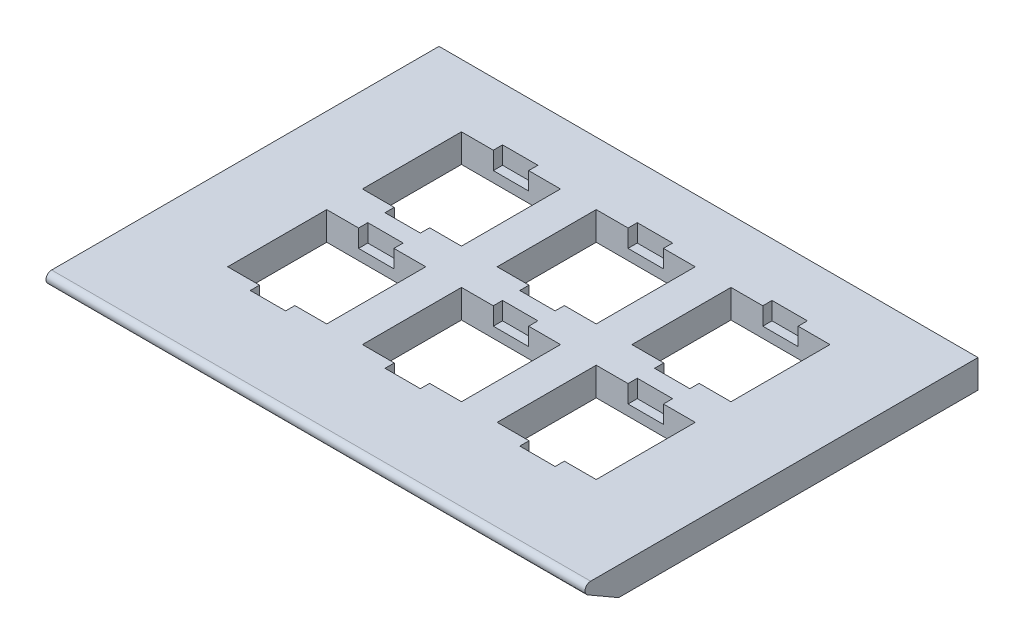
SolidWorks part; units mm, degrees
ref_plane "Front Plane" through (0, 0, 0) normal (0, 0, 1) x (1, 0, 0)
ref_plane "Top Plane" through (0, 0, 0) normal (0, 1, 0) x (1, 0, 0)
ref_plane "Right Plane" through (0, 0, 0) normal (1, 0, 0) x (0, 0, -1)
sketch "Sketch1" plane through (0, 0, 0) normal (0, 1, 0) x (1, 0, 0)
  line L1 (0, 0) -> (76.2, 0)
  line L2 (0, 0) -> (0, 50.8)
  line L3 (0, 50.8) -> (76.2, 50.8)
  line L4 (76.2, 0) -> (76.2, 50.8)
  dimension "D1" = 76.2
  dimension "D2" = 50.8
extrude "Boss-Extrude1" add sketch "Sketch1" against normal mid plane 4
sketch "Sketch2" plane through (0, 2, 0) normal (0, 1, 0) x (1, 0, 0)
  line L0 (0, 25.4) -> (76.2, 25.4) construction
  line L1 (12.051, 41.9245) -> (26.051, 41.9245)
  line L2 (12.051, 41.9245) -> (12.051, 27.9245)
  line L3 (12.051, 27.9245) -> (26.051, 27.9245)
  line L4 (26.051, 41.9245) -> (26.051, 27.9245)
  line L11 (0, 50.8) -> (0, 0) construction
  line L12 (76.2, 0) -> (76.2, 50.8) construction
  dimension "D1" = 14
  dimension "D2" = 12.051
  dimension "D3" = 2.5245
extrude "Cut-Extrude1" cut sketch "Sketch2" against normal through all both and the other way through all
sketch "Sketch3" plane through (0, 2, 0) normal (0, 1, 0) x (1, 0, 0)
  line L0 (12.051, 41.9245) -> (26.051, 41.9245) construction
  line L1 (16.5515, 41.9245) -> (21.5505, 41.9245)
  line L2 (16.5515, 41.9245) -> (16.5515, 43.2316)
  line L3 (16.5515, 43.2316) -> (21.5505, 43.2316)
  line L4 (21.5505, 41.9245) -> (21.5505, 43.2316)
  line L5 (12.051, 34.9245) -> (26.051, 34.9245) construction
  line L6 (12.051, 27.9245) -> (12.051, 41.9245) construction
  line L7 (26.051, 41.9245) -> (26.051, 27.9245) construction
  line L8 (16.5515, 26.6174) -> (21.5505, 26.6174)
  line L9 (21.5505, 27.9245) -> (21.5505, 26.6174)
  line L10 (16.5515, 27.9245) -> (21.5505, 27.9245)
  line L11 (16.5515, 27.9245) -> (16.5515, 26.6174)
  point P6 (19.051, 41.9245)
  point P7 (19.051, 43.2316)
  dimension "D1" = 4.999
  dimension "D2" = 1.3071
extrude "Cut-Extrude2" cut sketch "Sketch3" against normal blind 2.5001
pattern_linear "LPattern1" count 3 spacing 19.049 along (1, 0, 0) count 2 spacing 19.049 along (0, 0, 1) of "Cut-Extrude1", "Cut-Extrude2"
sketch "Sketch4" plane through (0, 0, 0) normal (-1, 0, 0) x (0, 0, 1)
  line L0 (0, -2) -> (6.9282, 2)
  line L1 (6.9282, 2) -> (0, 2)
  line L2 (-50.8, 2) -> (0, 2) construction
  line L3 (-50.8, -2) -> (0, -2) construction
  line L4 (0, 2) -> (0, -2)
  dimension "D1" = 30
extrude "Boss-Extrude2" add sketch "Sketch4" against normal up to surface (76.2 mm away) up to face at (76.2, 0, -25.4)
fillet "Fillet1" radius 0.7937 1 edges at (38.1, 2, 6.9282)
equation "\"D2@Sketch2\"=(3-2.0511in)/2"
equation "\"D3@Sketch2\"=.19878in/2"
